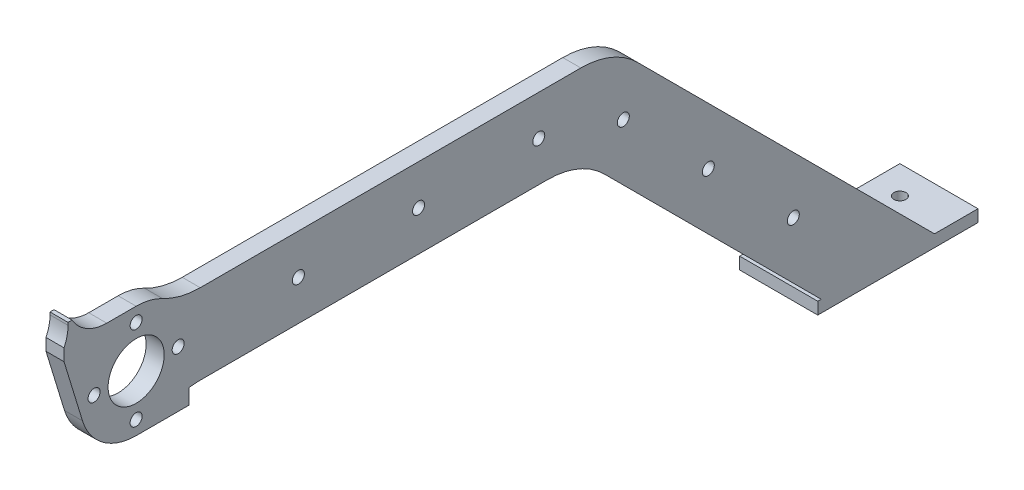
SolidWorks part; units mm, degrees
ref_plane "前视基准面" through (0, 0, 0) normal (0, 0, 1) x (1, 0, 0)
ref_plane "上视基准面" through (0, 0, 0) normal (0, 1, 0) x (1, 0, 0)
ref_plane "右视基准面" through (0, 0, 0) normal (1, 0, 0) x (0, 0, -1)
sketch "草图1" plane through (0, 0, 0) normal (1, 0, 0) x (0, 0, -1)
  line L2 (116.8579, -15.8579) -> (171, -70)
  line L3 (171, -70) -> (199.2843, -70)
  line L4 (199.2843, -70) -> (125.1421, 4.1421)
  line L5 (111, 10) -> (16, 10)
  line L7 (16, -10) -> (102.7369, -10)
  line L8 (186.193, -71.0509) -> (123.8062, -8.664) construction
  line L9 (0, 14) -> (-18, 14)
  line L10 (-18, 14) -> (-18, 11)
  line L11 (-18, 11) -> (-13.3889, -4.091)
  line L12 (13.2242, -14) -> (13.2242, -10)
  line L13 (0, -14) -> (13.2242, -14)
  arc A0 (6.5882, 12.3529) -> (6.5882, -12.3529) centre (0, 0) ccw
  circle A1 centre (0, 0) radius 10.5 construction
  circle A2 centre (0, 0) radius 7
  circle A3 centre (0, 10.5) radius 1.5
  circle A4 centre (10.5, 0) radius 1.5
  circle A5 centre (0, -10.5) radius 1.5
  circle A6 centre (-10.5, 0) radius 1.5
  arc A7 (125.1421, 4.1421) -> (111, 10) centre (111, -10) ccw
  arc A8 (102.7369, -10) -> (116.8579, -15.8579) centre (102.7157, -30) cw
  circle A9 centre (40.5, 0) radius 1.5
  circle A10 centre (70.5, 0) radius 1.5
  circle A11 centre (100.5, 0) radius 1.5
  circle A12 centre (121.61, -6.4679) radius 1.5
  circle A13 centre (142.8232, -27.6811) radius 1.5
  circle A14 centre (164.0364, -48.8943) radius 1.5
  arc A15 (16, 10) -> (6.5882, 12.3529) centre (16, 30) cw
  arc A16 (16, -10) -> (6.5882, -12.3529) centre (16, -30) ccw
  point P36 (185.1421, -70)
  point P43 (9.798, 7.7889)
  point P50 (9.798, -10)
  dimension "D1" = 28
  dimension "D2" = 21
  dimension "D3" = 14
  dimension "D4" = 3
  dimension "D9" = 20
  dimension "D13" = 3
  dimension "D16" = 30
  dimension "D17" = 3
  dimension "D19" = 30
  dimension "D24" = 20
  dimension "D25" = 20
  dimension "D6" = 135
  dimension "D7" = 20
  dimension "D8" = 171
  dimension "D10" = 70
  dimension "D11" = 20
  dimension "D14" = 40.5
  dimension "D18" = 21.11
  dimension "D20" = 30
  dimension "D21" = 18
  dimension "D22" = 3
  dimension "D26" = 13.2242
  dimension "D28" = 20
  dimension "D15" = 3
  dimension "D5" = 4
extrude "凸台-拉伸1" add sketch "草图1" along normal mid plane 4.5 contours A16 L7 A8 L2 L3 L4 A7 L5 A15 A0 A14 A13 A12 A11 A10 A9 A6 A5 A4 A3 A2 | A0 L9 L10 L11 | L12 A16 A0 region at (0, -9.4091, -111.2575) region at (0, -12.6228, -9.4909) region at (0, 9.7023, 13.097)
sketch "草图3" plane through (0, -70, 0) normal (0, -1, 0) x (1, 0, 0)
  line L0 (2.25, -116.8579) -> (2.25, -171) construction
  line L1 (2.25, -170.1443) -> (-17.25, -170.1443)
  line L2 (2.25, -170.1443) -> (2.25, -210.1443)
  line L3 (2.25, -210.1443) -> (-17.25, -210.1443)
  line L4 (-17.25, -170.1443) -> (-17.25, -210.1443)
  dimension "D1" = 19.5
  dimension "D2" = 40
  dimension "D3" = 10.86
extrude "凸台-拉伸2" add sketch "草图3" along normal blind 3
sketch "草图4" plane through (0, -70, 0) normal (0, 1, 0) x (1, 0, 0)
  line L0 (-17.25, 190.1443) -> (2.25, 190.1443) construction
  line L1 (-17.25, 170.1443) -> (-17.25, 210.1443) construction
  line L2 (2.25, 199.2843) -> (2.25, 125.1421) construction
  line L3 (-17.25, 210.1443) -> (2.25, 210.1443) construction
  circle A0 centre (-10.25, 203.1443) radius 1.5
  circle A1 centre (-10.25, 177.1443) radius 1.5
  dimension "D1" = 3
  dimension "D2" = 7
  dimension "D3" = 7
extrude "切除-拉伸1" cut sketch "草图4" against normal through all
sketch "草图5" plane through (-2.25, 0, 0) normal (-1, 0, 0) x (0, 0, 1)
  line L1 (0, 14) -> (18, 14) construction
  line L2 (16.9982, 14) -> (16.9982, 19.003)
  line L3 (16.9982, 19.003) -> (15.9937, 19.003)
  line L4 (15.9937, 19.003) -> (15.9937, 14)
  line L5 (15.9937, 14) -> (16.9982, 14)
extrude "凸台-拉伸3" add sketch "草图5" against normal up to vertex (4.5 mm away) up to point (2.25, 14, 18)
fillet "圆角1" radius 10 2 edges at (0, 14, 15.9937) (0, 14, 16.9982)
